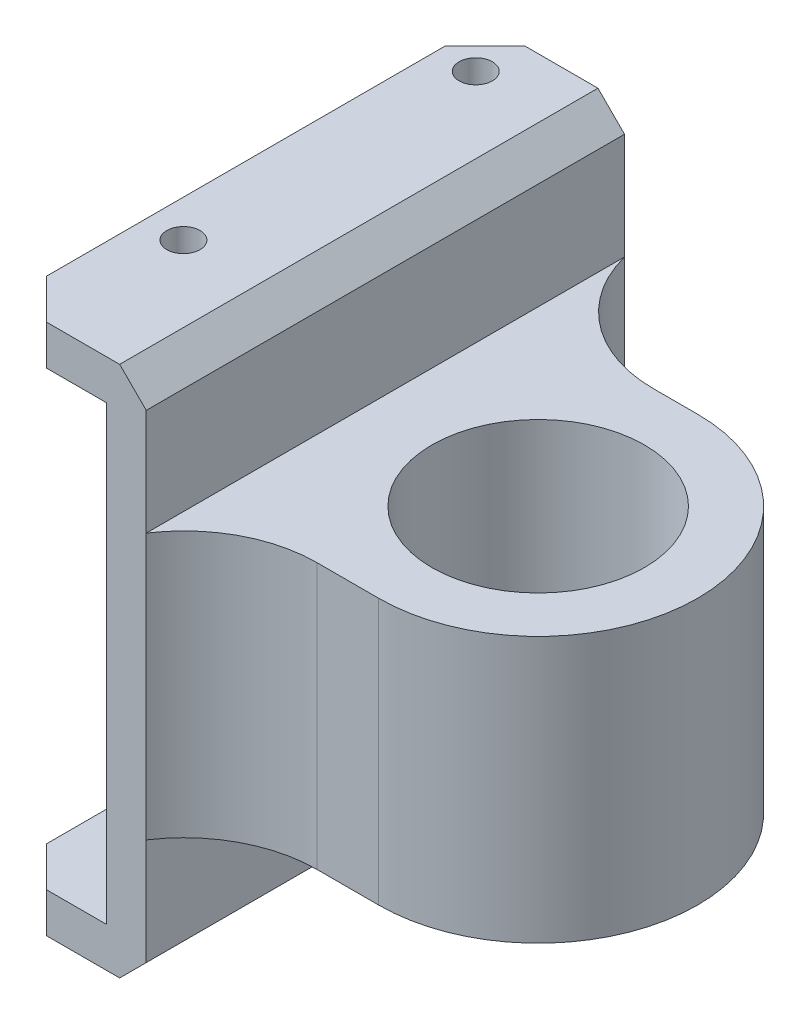
SolidWorks part; units mm, degrees
material "3003 Alloy"
ref_plane "Front Plane" through (0, 0, 0) normal (0, 0, 1) x (1, 0, 0)
ref_plane "Top Plane" through (0, 0, 0) normal (0, 1, 0) x (1, 0, 0)
ref_plane "Right Plane" through (0, 0, 0) normal (1, 0, 0) x (0, 0, -1)
sketch "Sketch1" plane through (0, 0, 0) normal (0, 0, 1) x (1, 0, 0)
  line L0 (-10.5, 17) -> (-3, 17)
  line L1 (-10.5, 20) -> (0, 20)
  line L2 (-3, 17) -> (-3, -17)
  line L3 (-10.5, -20) -> (0, -20)
  line L4 (0, 20) -> (0, -20)
  line L5 (-10.5, -17) -> (-3, -17)
  line L6 (-10.5, 20) -> (-10.5, 17)
  line L7 (-10.5, -17) -> (-10.5, -20)
  dimension "D2" = 34
  dimension "D3" = 10.5
  dimension "D1" = 3
extrude "Boss-Extrude1" add sketch "Sketch1" along normal blind 36
sketch "Sketch2" plane through (0, 20, 0) normal (0, 1, 0) x (1, 0, 0)
  line L0 (-7.7, -3.5) -> (-7.7, -25.5) construction
  line L1 (-10.5, -36) -> (-10.5, 0) construction
  line L2 (0, 0) -> (-10.5, 0) construction
  circle A0 centre (-7.7, -3.5) radius 1.25
  circle A1 centre (-7.7, -25.5) radius 1.25
  dimension "D1" = 22
  dimension "D2" = 2.5
  dimension "D4" = 3.5
  dimension "D3" = 2.8
extrude "Cut-Extrude1" cut sketch "Sketch2" against normal through all
chamfer "Chamfer1" distance 3 angle 45 4 edges at (-10.5, -18.5, 36) (-10.5, -18.5, 0) (-10.5, 18.5, 36) (-10.5, 18.5, 0)
sketch "Sketch4" plane through (0, 20, 0) normal (0, 1, 0) x (1, 0, 0)
  line L0 (13, -7.5) -> (0, -7.5)
  line L1 (0, -36) -> (0, 0) construction
  line L2 (13, -31.5) -> (0, -31.5)
  line L3 (0, -31.5) -> (0, -7.5)
  line L4 (0, 0) -> (-7.5, 0) construction
  circle A0 centre (13, -19.5) radius 8
  arc A1 (13, -31.5) -> (13, -7.5) centre (13, -19.5) ccw
  dimension "D1" = 16
  dimension "D2" = 24
  dimension "D3" = 19.5
  dimension "D4" = 13
extrude "Boss-Extrude2" add sketch "Sketch4" against normal through all
fillet "Fillet1" radius 10 2 edges
sketch "Sketch5" plane through (0, 0, 36) normal (0, 0, 1) x (1, 0, 0)
  line L0 (25, -20) -> (25, 20) construction
  line L1 (0, 20) -> (25, 20)
  line L2 (0, 20) -> (0, 10)
  line L3 (0, 10) -> (25, 10)
  line L4 (25, 20) -> (25, 10)
  line L5 (0, 0) -> (25, 0) construction
  line L6 (0, -20) -> (25, -20)
  line L7 (25, -20) -> (25, -10)
  line L8 (0, -10) -> (25, -10)
  line L9 (0, -20) -> (0, -10)
  dimension "D1" = 20
extrude "Cut-Extrude3" cut sketch "Sketch5" against normal through all
chamfer "Chamfer2" distance 2 angle 45 2 edges at (0, -20, 18) (0, 20, 18)
